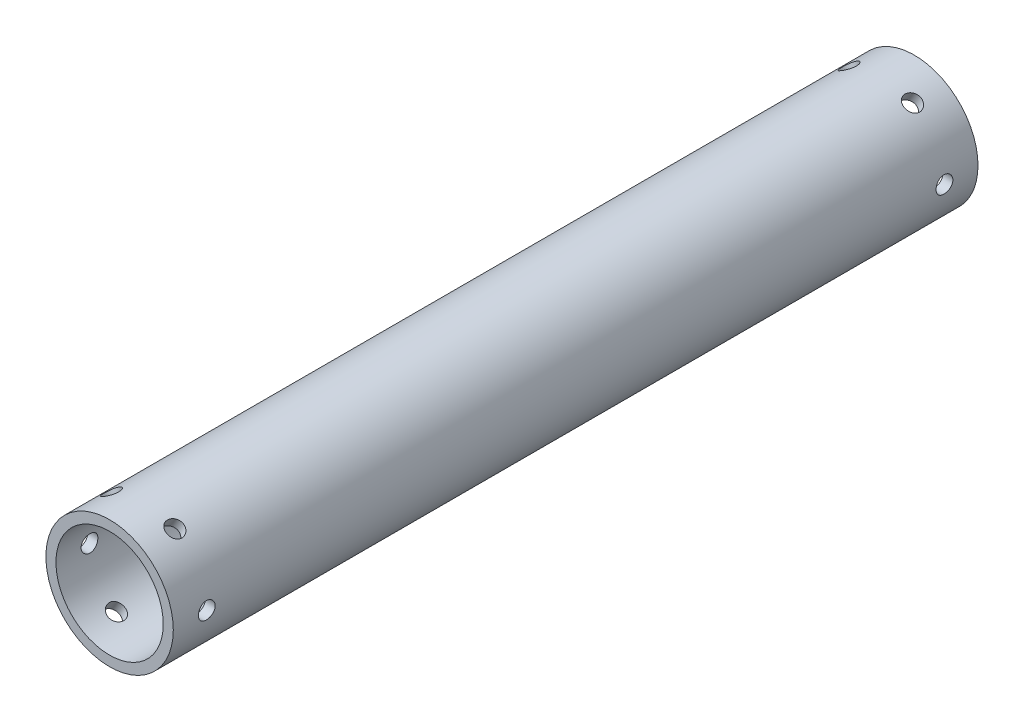
SolidWorks part; units mm, degrees
ref_plane "Front Plane" through (0, 0, 0) normal (1, 0, 0) x (0, 1, 0)
ref_plane "Top Plane" through (0, 0, 0) normal (0, 0, 1) x (0, 1, 0)
ref_plane "Right Plane" through (0, 0, 0) normal (0, 1, 0) x (-1, 0, 0)
sketch "Sketch2" plane through (0, 0, 0) normal (0, 0, 1) x (0, 1, 0)
  line L0 (0, 0) -> (24.13, 0) construction
  circle A0 centre (0, 0) radius 24.13
  circle A1 centre (0, 0) radius 20.32
  dimension "D1" = 40.64
  dimension "D2" = 3.81
extrude "base" add sketch "Sketch2" along normal blind 304.8
ref_plane "Plane1" through (24.13, 0, 0) normal (1, 0, 0) x (0, 0, -1)
sketch "Sketch3" plane through (24.13, 0, 0) normal (1, 0, 0) x (0, 0, -1)
  line L0 (0, 0) -> (-304.8, 0) construction
  line L1 (0, 24.13) -> (0, -24.13) construction
  line L2 (-304.8, 24.13) -> (-304.8, -24.13) construction
  line L3 (0, 0) -> (0, 24.13) construction
  circle A0 centre (-12.7, 0) radius 3.175
  circle A1 centre (-292.1, 0) radius 3.175
  dimension "D1" = 6.35
  dimension "D3" = 6.35
  dimension "D2" = 12.7
  dimension "D4" = 12.7
extrude "boltholes" cut sketch "Sketch3" against normal up to next
pattern_circular "CirPattern1" count 6 over 360 about axis through (0, 0, 304.8) along (0, 0, -1) of "boltholes" reverse direction yes
